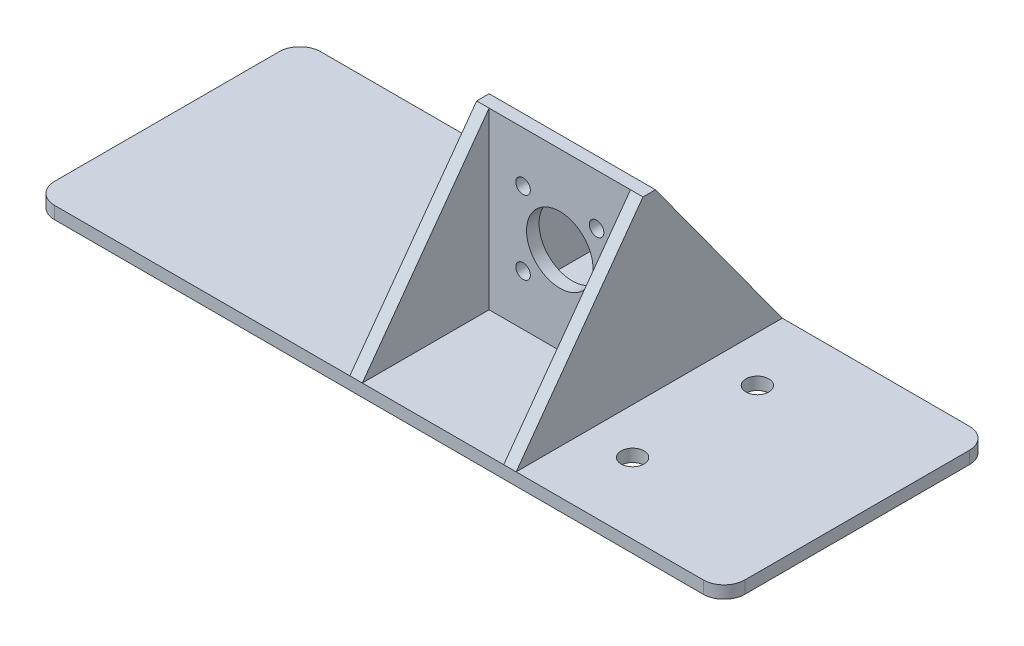
SolidWorks part; units mm, degrees
material "ABS PC"
ref_plane "Front Plane" through (0, 0, 0) normal (0, 0, 1) x (1, 0, 0)
ref_plane "Top Plane" through (0, 0, 0) normal (0, 1, 0) x (1, 0, 0)
ref_plane "Right Plane" through (0, 0, 0) normal (1, 0, 0) x (0, 0, -1)
sketch "Sketch1" plane through (0, 0, 0) normal (0, 1, 0) x (1, 0, 0)
  line L1 (78, 32) -> (-78, 32)
  line L2 (83, 27) -> (83, -27)
  line L3 (78, -32) -> (-78, -32)
  line L4 (-83, 27) -> (-83, -27)
  line L5 (83, 32) -> (-83, -32) construction
  line L6 (83, -32) -> (-83, 32) construction
  arc A0 (78, 32) -> (83, 27) centre (78, 27) cw
  arc A1 (83, -27) -> (78, -32) centre (78, -27) cw
  arc A2 (-78, -32) -> (-83, -27) centre (-78, -27) cw
  arc A3 (-78, 32) -> (-83, 27) centre (-78, 27) ccw
  point P0 (0, 0)
  dimension "D1" = 5
  dimension "D2" = 166
  dimension "D3" = 64
extrude "Boss-Extrude1" add sketch "Sketch1" along normal blind 3
sketch "Sketch2" plane through (0, 3, 0) normal (0, 1, 0) x (1, 0, 0)
  line L0 (-83, 0) -> (83, 0) construction
  line L1 (-83, 27) -> (-83, -27) construction
  line L2 (83, -27) -> (83, 27) construction
  circle A0 centre (44, -15) radius 2.75
  circle A1 centre (44, 15) radius 2.75
  circle A2 centre (-18, 0) radius 2.75
  dimension "D1" = 30
  dimension "D3" = 5.5
  dimension "D4" = 62
  dimension "D2" = 127
extrude "Cut-Extrude1" cut sketch "Sketch2" against normal through all
sketch "Sketch3" plane through (0, 3, 0) normal (0, 1, 0) x (1, 0, 0)
  line L0 (-78, -32) -> (78, -32) construction
  line L1 (-7, 32) -> (33, 32) construction
  line L2 (-7, 0) -> (-7, -32) construction
  line L3 (-7, -32) -> (33, -32) construction
  line L4 (33, -15) -> (33, -32) construction
  line L5 (78, 32) -> (-78, 32) construction
  line L6 (44, -15) -> (33, -15) construction
  line L7 (-18, 0) -> (-7, 0) construction
  line L8 (-7, 32) -> (-7, 0) construction
  line L9 (33, 32) -> (33, -15) construction
  line L11 (-7, 1.5) -> (33, 1.5)
  line L12 (-7, 1.5) -> (-7, -1.5)
  line L13 (-7, -1.5) -> (33, -1.5)
  line L14 (33, 1.5) -> (33, -1.5)
  point P18 (0, 0)
  point P19 (-7, 0)
  point P20 (0, 0)
  dimension "D1" = 40
  dimension "D2" = 3
extrude "Boss-Extrude2" add sketch "Sketch3" along normal blind 42
sketch "Sketch6" plane through (0, 0, -1.5) normal (0, 0, -1) x (-1, 0, 0)
  line L0 (-13, 45) -> (-13, 3) construction
  line L1 (-33, 45) -> (7, 45) construction
  line L2 (-33, 3) -> (7, 3) construction
  line L3 (-13, 24) -> (-4.1612, 15.1612) construction
  line L4 (-33, 45) -> (-33, 3) construction
  line L5 (-33, 24) -> (7, 24) construction
  line L6 (7, 45) -> (7, 3) construction
  circle A0 centre (-13, 24) radius 8
  circle A1 centre (-4.1612, 15.1612) radius 1.75
  circle A2 centre (-21.8388, 15.1612) radius 1.75
  circle A3 centre (-21.8388, 32.8388) radius 1.75
  circle A4 centre (-4.1612, 32.8388) radius 1.75
  dimension "D1" = 16
  dimension "D3" = 3.5
  dimension "D2" = 12.5
  dimension "D4" = 45
extrude "Cut-Extrude2" cut sketch "Sketch6" against normal through all both
sketch "Sketch7" plane through (0, 0, -1.5) normal (0, 0, -1) x (-1, 0, 0)
  line L0 (-33, 3) -> (7, 3) construction
  line L1 (-33, 45) -> (-30, 45)
  line L2 (-33, 45) -> (-33, 3)
  line L3 (-33, 3) -> (-30, 3)
  line L4 (-30, 45) -> (-30, 3)
  line L5 (-78, 3) -> (78, 3) construction
  line L6 (7, 45) -> (4, 45)
  line L7 (7, 45) -> (7, 3)
  line L8 (7, 3) -> (4, 3)
  line L9 (4, 45) -> (4, 3)
  dimension "D1" = 3
  dimension "D2" = 3
extrude "Boss-Extrude3" add sketch "Sketch7" along normal blind 30.5 and the other way blind 33.5
sketch "Sketch8" plane through (-7, 0, 0) normal (-1, 0, 0) x (0, 0, 1)
  line L0 (-1.5, 45) -> (-32, 3)
  line L1 (-32, 3) -> (-32, 45)
  line L2 (-32, 45) -> (-1.5, 45)
  line L3 (1.5, 45) -> (32, 3)
  line L4 (32, 3) -> (32, 45)
  line L5 (32, 45) -> (1.5, 45)
extrude "Cut-Extrude5" cut sketch "Sketch8" against normal through all both
